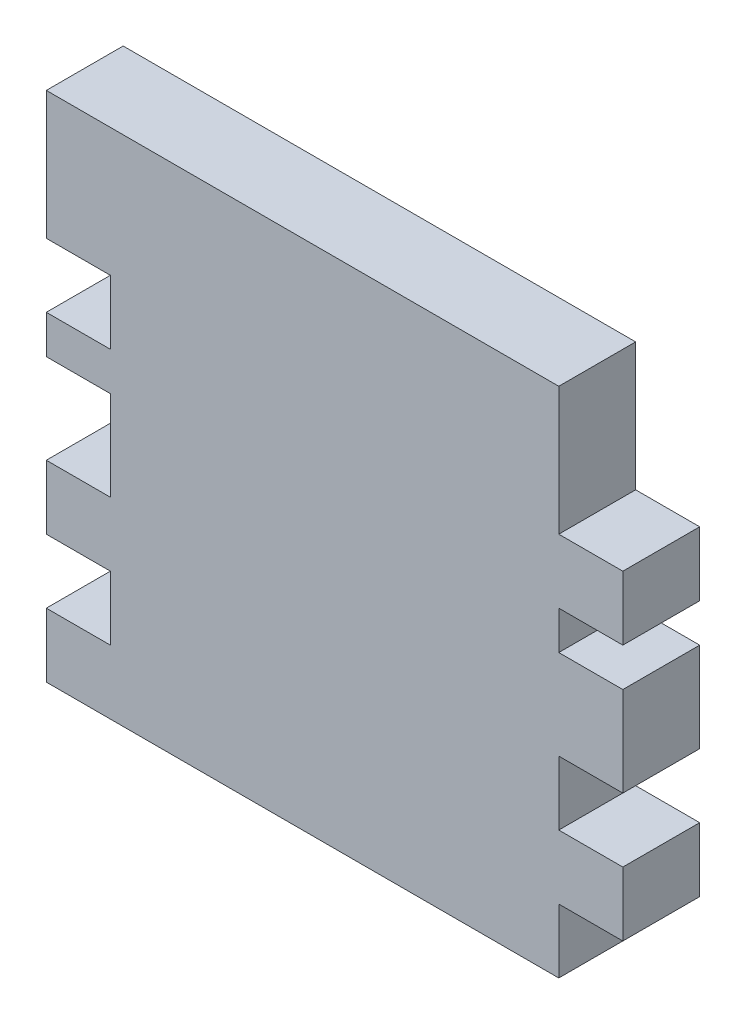
SolidWorks part; units mm, degrees
ref_plane "Front Plane" through (0, 0, 0) normal (0, 0, 1) x (1, 0, 0)
ref_plane "Top Plane" through (0, 0, 0) normal (0, 1, 0) x (1, 0, 0)
ref_plane "Right Plane" through (0, 0, 0) normal (1, 0, 0) x (0, 0, -1)
sketch "Sketch1" plane through (0, 0, 0) normal (0, 0, 1) x (1, 0, 0)
  line L1 (-18.4337, 17.4849) -> (26.5663, 17.4849)
  line L2 (-18.4337, 17.4849) -> (-18.4337, -22.5151)
  line L3 (-18.4337, -22.5151) -> (26.5663, -22.5151)
  line L4 (26.5663, 17.4849) -> (26.5663, -22.5151)
  dimension "D1" = 45
  dimension "D2" = 40
extrude "Boss-Extrude1" add sketch "Sketch1" along normal blind 6 contours L2 L1 L4 L3
sketch "Sketch2" plane through (0, 0, 6) normal (0, 0, 1) x (1, 0, 0)
  line L0 (-18.4337, 17.4849) -> (-18.4337, -22.5151) construction
  line L1 (-18.4337, 7.4849) -> (-13.4337, 7.4849)
  line L2 (-18.4337, 7.4849) -> (-18.4337, 2.4849)
  line L3 (-18.4337, 2.4849) -> (-13.4337, 2.4849)
  line L4 (-13.4337, 7.4849) -> (-13.4337, 2.4849)
  line L5 (-18.4337, 17.4849) -> (26.5663, 17.4849) construction
  line L6 (-18.4337, -2.5151) -> (-13.4337, -2.5151)
  line L7 (-18.4337, -2.5151) -> (-18.4337, -9.5151)
  line L8 (-18.4337, -9.5151) -> (-13.4337, -9.5151)
  line L9 (-13.4337, -2.5151) -> (-13.4337, -9.5151)
  line L10 (-18.4337, -12.5151) -> (-13.4337, -12.5151)
  line L11 (-18.4337, -12.5151) -> (-18.4337, -17.5151)
  line L12 (-18.4337, -17.5151) -> (-13.4337, -17.5151)
  line L13 (-13.4337, -12.5151) -> (-13.4337, -17.5151)
  line L14 (-18.4337, -22.5151) -> (26.5663, -22.5151) construction
  dimension "D1" = 5
  dimension "D2" = 5
  dimension "D3" = 5
  dimension "D4" = 5
  dimension "D5" = 10
  dimension "D6" = 5
  dimension "D7" = 5
  dimension "D8" = 5
  dimension "D9" = 7
extrude "Cut-Extrude1" cut sketch "Sketch2" against normal blind 6 contours L2 L1 L4 L3 | L7 L6 L9 L8 | L11 L10 L13 L12
sketch "Sketch3" plane through (0, 0, 6) normal (0, 0, 1) x (1, 0, 0)
  line L0 (26.5663, 17.4849) -> (26.5663, -22.5151) construction
  line L1 (21.5663, 2.4849) -> (26.5663, 2.4849)
  line L2 (21.5663, 2.4849) -> (21.5663, 7.4849)
  line L3 (21.5663, 7.4849) -> (26.5663, 7.4849)
  line L4 (26.5663, 2.4849) -> (26.5663, 7.4849)
  line L6 (26.5663, -0.5151) -> (21.5663, -0.5151)
  line L7 (26.5663, -0.5151) -> (26.5663, -7.5151)
  line L8 (26.5663, -7.5151) -> (21.5663, -7.5151)
  line L9 (21.5663, -0.5151) -> (21.5663, -7.5151)
  line L10 (26.5663, -12.5151) -> (21.5663, -12.5151)
  line L11 (26.5663, -12.5151) -> (26.5663, -17.5151)
  line L12 (26.5663, -17.5151) -> (21.5663, -17.5151)
  line L13 (21.5663, -12.5151) -> (21.5663, -17.5151)
  line L16 (21.5663, 7.4849) -> (26.5663, 7.4849)
  line L17 (21.5663, 7.4849) -> (21.5663, 17.4849)
  line L18 (21.5663, 17.4849) -> (26.5663, 17.4849)
  line L19 (26.5663, 7.4849) -> (26.5663, 17.4849)
  line L20 (21.5663, -0.5151) -> (26.5663, -0.5151)
  line L21 (21.5663, -0.5151) -> (21.5663, 2.4849)
  line L22 (21.5663, 2.4849) -> (26.5663, 2.4849)
  line L23 (26.5663, -0.5151) -> (26.5663, 2.4849)
  line L24 (21.5663, -12.5151) -> (26.5663, -12.5151)
  line L25 (21.5663, -12.5151) -> (21.5663, -7.5151)
  line L26 (21.5663, -7.5151) -> (26.5663, -7.5151)
  line L27 (26.5663, -12.5151) -> (26.5663, -7.5151)
  line L28 (21.5663, -17.5151) -> (26.5663, -17.5151)
  line L29 (21.5663, -17.5151) -> (21.5663, -22.5151)
  line L30 (21.5663, -22.5151) -> (26.5663, -22.5151)
  line L31 (26.5663, -17.5151) -> (26.5663, -22.5151)
  line M19 (-18.4337, -22.5151) -> (26.5663, -22.5151)
  line M20 (26.5663, -22.5151) -> (26.5663, 17.4849)
  line M21 (26.5663, 17.4849) -> (-18.4337, 17.4849)
  dimension "D1" = 5
  dimension "D4" = 5
  dimension "D6" = 5
  dimension "D7" = 7
extrude "Cut-Extrude3" cut sketch "Sketch3" against normal blind 6 contours L10 L13 L12 M20 | L6 L9 L8 M20 | L3 L2 L1 M20 region at (24.0663, 4.9849, 6) region at (24.0663, -4.0151, 6) region at (24.0663, -15.0151, 6)
extrude "Boss-Extrude3" add sketch "Sketch3<4>" against normal blind 6 contours L3 L2 L1 M20 | L6 L9 L8 M20 | L10 L13 L12 M20 region at (24.0663, 4.9849, 6) region at (24.0663, -4.0151, 6) region at (24.0663, -15.0151, 6)
sketch "Sketch3<4>" plane through (0, 0, 6) normal (0, 0, 1) x (1, 0, 0) same geometry as "Sketch3"
extrude "Cut-Extrude4" cut sketch "Sketch3<5>" against normal blind 6 contours L17 L3 M20 M21 | L21 L6 L1 M20 | L25 L10 L8 M20 | L12 L29 M19 M20 region at (24.0663, 0.9849, 6) region at (24.0663, 12.4849, 6) region at (24.0663, -10.0151, 6) region at (24.0663, -20.0151, 6)
sketch "Sketch3<5>" plane through (0, 0, 6) normal (0, 0, 1) x (1, 0, 0) same geometry as "Sketch3"
sketch "Sketch4" plane through (0, 0, 6) normal (0, 0, 1) x (1, 0, 0)
  line L1 (-18.4337, 2.4849) -> (-13.4337, 2.4849)
  line L2 (-18.4337, 2.4849) -> (-18.4337, -0.5151)
  line L3 (-18.4337, -0.5151) -> (-13.4337, -0.5151)
  line L4 (-13.4337, 2.4849) -> (-13.4337, -0.5151)
  line L5 (-18.4337, -0.5151) -> (-13.4337, -0.5151)
  line L6 (-18.4337, -0.5151) -> (-18.4337, -7.5151)
  line L7 (-18.4337, -7.5151) -> (-13.4337, -7.5151)
  line L8 (-13.4337, -0.5151) -> (-13.4337, -7.5151)
  line L10 (-18.4337, -9.5151) -> (-18.4337, -12.5151) construction
  line L11 (-13.4337, -7.5151) -> (-18.4337, -7.5151)
  line L12 (-13.4337, -7.5151) -> (-13.4337, -12.5151)
  line L13 (-13.4337, -12.5151) -> (-18.4337, -12.5151)
  line L14 (-18.4337, -7.5151) -> (-18.4337, -12.5151)
  line M11 (-18.4337, 2.4849) -> (-18.4337, -2.5151)
  line M12 (-18.4337, -2.5151) -> (-13.4337, -2.5151)
  dimension "D1" = 3
  dimension "D2" = 5
  dimension "D3" = 7
  dimension "D4" = 5
extrude "Cut-Extrude10" cut sketch "Sketch4" against normal blind 10 contours L8 L3 M11 M12 region at (-15.9337, -1.5151, 6)
sketch "Sketch5" plane through (0, 0, 6) normal (0, 0, 1) x (1, 0, 0)
  line L0 (-13.4337, -0.5151) -> (-13.4337, -9.5151) construction
  line L1 (-18.4337, -12.5151) -> (-13.4337, -12.5151)
  line L2 (-18.4337, -12.5151) -> (-18.4337, -7.5151)
  line L3 (-18.4337, -7.5151) -> (-13.4337, -7.5151)
  line L4 (-13.4337, -12.5151) -> (-13.4337, -7.5151)
  dimension "D1" = 5
extrude "Boss-Extrude4" add sketch "Sketch5" against normal blind 6 contours L2 L1 L4 L3
